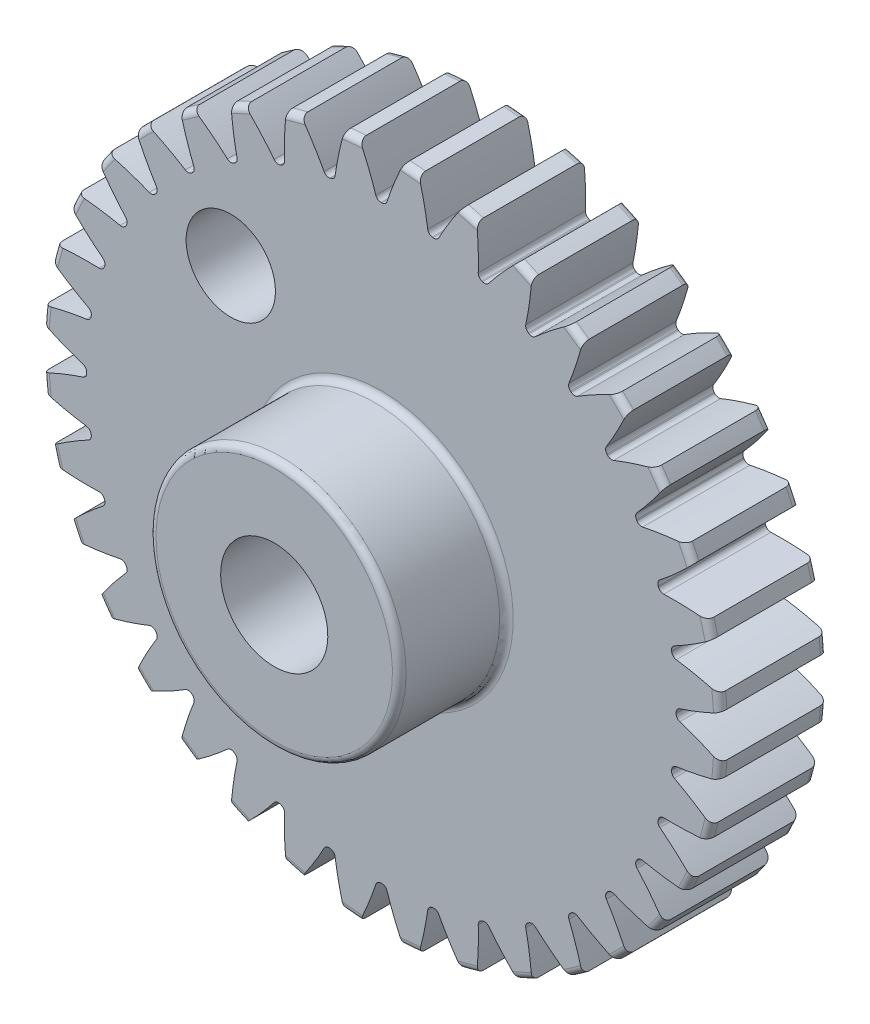
SolidWorks part; units mm, degrees
material "Delrin 2700 NC010, Low Viscosity Acetal Copolymer (SS)"
ref_plane "Front Plane" through (0, 0, 0) normal (0, 0, 1) x (1, 0, 0)
ref_plane "Top Plane" through (0, 0, 0) normal (0, 1, 0) x (1, 0, 0)
ref_plane "Right Plane" through (0, 0, 0) normal (1, 0, 0) x (0, 0, -1)
sketch "Sketch1" plane through (0, 0, 0) normal (0, 0, 1) x (1, 0, 0)
  line L0 (-457.2, 0) -> (457.2, 0) construction
  circle A0 centre (0, 0) radius 19 construction
  circle A1 centre (0, 0) radius 18 construction
  circle A2 centre (0, 0) radius 16.5 construction
  circle A3 centre (0, 0) radius 7 construction
  circle A4 centre (0, 0) radius 3 construction
  dimension "D2" = 1
  dimension "D3" = 2.5
  dimension "D1" = 2.5
sketch "Sketch2" plane through (0, 0, 0) normal (1, 0, 0) x (0, 0, -1)
  line L0 (0, 0) -> (-6, 0) construction
  line L1 (-6, 0) -> (-12, 0) construction
  dimension "Overall Width" = 12
  dimension "Face Width" = 6
sketch "Sketch4" plane through (0, 0, 0) normal (1, 0, 0) x (0, 0, -1)
  line L0 (-12, 3) -> (-12, 7)
  line L1 (-12, 7) -> (-6, 7)
  line L2 (-6, 7) -> (-6, 19)
  line L3 (-6, 19) -> (0, 19)
  line L4 (0, 19) -> (0, 3)
  line L5 (-6, 7) -> (-6, 0) construction
  line L6 (0, 19) -> (0, -19) construction
  line L7 (-6, 7) -> (0, 7) construction
  line L12 (-12, 3) -> (0, 3)
revolve "Revolve1" add sketch "Sketch4" angle 360 about L1
fillet "Fillet2" radius 0.38 4 edges at (0, 7, 12) (0, 7, 6) (0, 19, 6) (0, 19, 0)
sketch "Sketch7" plane through (0, 0, 6) normal (0, 0, 1) x (1, 0, 0)
  line L0 (0, 0) -> (0, 19) construction
  line L1 (0.7851, 17.9829) -> (1.191, 18.9626) construction
  line L3 (1.656, 18.9277) -> (1.5688, 17.9315) construction
  line L4 (1.5688, 17.9315) -> (1.4381, 16.4372) construction
  line L5 (0, 0) -> (1.4381, 16.4372) construction
  line L6 (0.7851, 17.9829) -> (0, 0) construction
  line L7 (0.7851, 17.9829) -> (0.8288, 18.9819) construction
  line L8 (0.7851, 17.9829) -> (0, 0) construction
  circle A0 centre (0, 0) radius 19 construction
  arc A1 (-0.0266, 16.5) -> (0.0266, 16.5) centre (0, 0) cw
  circle A2 centre (0, 0) radius 16.5 construction
  arc A3 (-0.7851, 17.9829) -> (0.7851, 17.9829) centre (0, 0) cw construction
  circle A4 centre (0, 0) radius 18 construction
  arc A5 (2.0864, 18.8851) -> (1.2246, 18.9605) centre (0, 0) ccw construction
  arc A6 (0.7851, 17.9829) -> (2.3495, 17.846) centre (0, 0) cw construction
  arc A7 (-1.2246, 18.9605) -> (1.2246, 18.9605) centre (0, 0) cw
  arc A8 (0.3122, 16.7065) -> (1.2246, 18.9605) centre (17.415, 11.0946) cw
  arc A9 (-0.3122, 16.7065) -> (-1.2246, 18.9605) centre (-17.415, 11.0946) ccw
  arc A10 (-0.0266, 16.5) -> (-0.3122, 16.7065) centre (-0.0271, 16.8) cw
  arc A11 (0.0266, 16.5) -> (0.3122, 16.7065) centre (0.0271, 16.8) ccw
  point P26 (-0.2452, 16.4982)
  point P29 (0.2452, 16.4982)
  dimension "D4" = 0.3
  dimension "D5" = 18
  dimension "D3" = 20
  dimension "D1" = 3.1416
  dimension "D2" = 1.5708
extrude "Cut-Extrude2" cut sketch "Sketch7" against normal through all
pattern_circular "CirPattern1" count 36 over 360 about axis through (0, 0, 12) along (0, 0, -1) of "Cut-Extrude2"
sketch "Sketch8" plane through (0, 0, 6) normal (0, 0, 1) x (1, 0, 0)
  circle A0 centre (-8.4327, 9.2271) radius 2.5
  circle A1 centre (0, 0) radius 3 construction
  dimension "D1" = 5
  dimension "D2" = 12.5
extrude "Cut-Extrude3" cut sketch "Sketch8" against normal through all
equation "\"D1@Sketch1\"=2.5*(\"Pitch Dia.@Sketch1\"/\"Number of Teeth@Sketch1\")"
equation "\"D1@CirPattern1\"=\"Number of Teeth@Sketch1\""
equation "\"D1@Fillet2\"=\"OD@Sketch1\"*.01"
equation "\"D1@Sketch7\"=3.14159*(\"Pitch Dia.@Sketch1\"/\"Number of Teeth@Sketch1\")"
equation "\"D2@Sketch7\"=\"D1@Sketch7\"/2"
equation "\"D4@Sketch7\"=\"D1@Sketch7\"*.0955"
equation "\"D5@Sketch7\"=\"Pitch Dia.@Sketch1\"/2"
